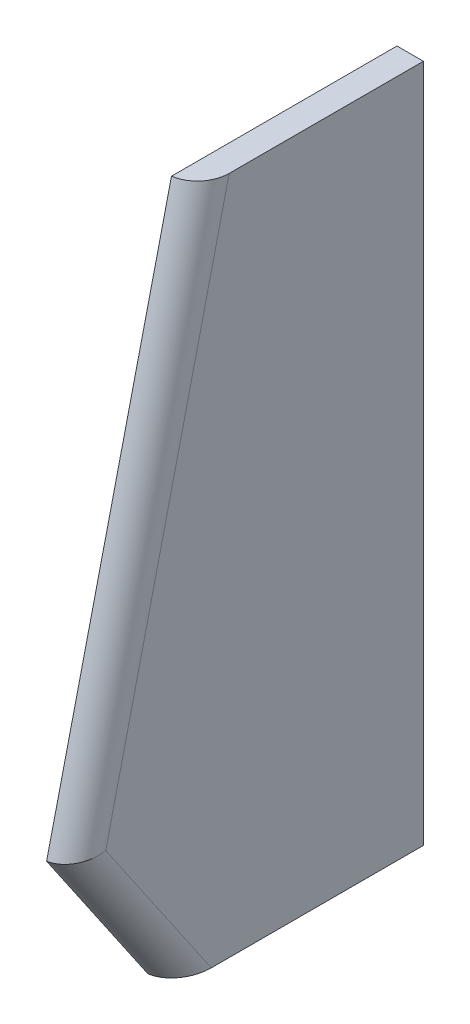
SolidWorks part; units mm, degrees
ref_plane "Front Plane" through (0, 0, 0) normal (0, 0, 1) x (1, 0, 0)
ref_plane "Top Plane" through (0, 0, 0) normal (0, 1, 0) x (1, 0, 0)
ref_plane "Right Plane" through (0, 0, 0) normal (1, 0, 0) x (0, 0, -1)
sketch "Sketch1" plane through (0, 0, 0) normal (1, 0, 0) x (0, 0, -1)
  line L0 (-20.4184, -27.6487) -> (20.2216, 145.0713)
  line L1 (20.2216, 145.0713) -> (93.5922, 145.0713)
  line L2 (93.5922, 145.0713) -> (93.5922, -75.9087) construction
  line L3 (93.5922, -75.9087) -> (12.5874, -75.9087)
  line L4 (12.5874, -75.9087) -> (-20.4184, -27.6487)
  line L5 (-20.4184, -27.6487) -> (93.5816, -27.6487)
  line L6 (93.5816, -27.6487) -> (93.5922, 145.0713)
  line L7 (93.5816, -27.6487) -> (93.5922, -75.9087)
  dimension "D1" = 114.0106
  dimension "D2" = 73.3706
  dimension "D3" = 81.0048
  dimension "D4" = 48.26
  dimension "D5" = 172.72
extrude "Boss-Extrude1" add sketch "Sketch1" along normal blind 8.6 contours L5 L6 L1 L0 | L7 L5 L4 L3 region at (0, -50.4178, -44.3702) region at (0, 52.4692, -46.0097)
fillet "Fillet1" radius 10 2 edges at (8.6, -51.7787, 3.9155) (8.6, 58.7113, 0.0984)
